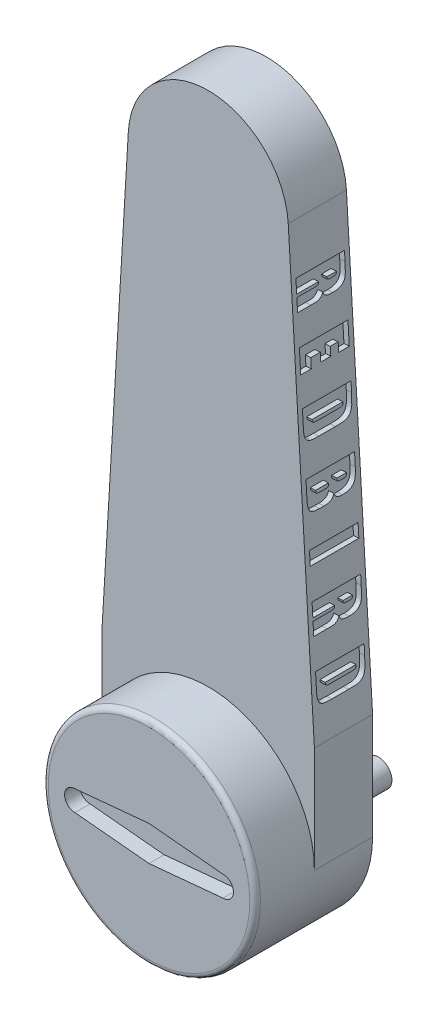
SolidWorks part; units mm, degrees
ref_plane "Front Plane" through (0, 0, 0) normal (0, 0, 1) x (1, 0, 0)
ref_plane "Top Plane" through (0, 0, 0) normal (0, 1, 0) x (1, 0, 0)
ref_plane "Right Plane" through (0, 0, 0) normal (1, 0, 0) x (0, 0, -1)
sketch "Sketch2" plane through (0, 0, 0) normal (0, 0, 1) x (1, 0, 0)
  circle A0 centre (0, 0) radius 39.75
  dimension "D1" = 79.5
extrude "Boss-Extrude1" add sketch "Sketch2" along normal blind 44
sketch "Sketch3" plane through (0, 0, 0) normal (0, 1, 0) x (1, 0, 0)
  line L0 (39.75, -44) -> (39.75, 0) construction
  line L1 (-39.75, 0) -> (39.75, 0)
  line L2 (-39.75, 0) -> (-39.75, -21.8)
  line L3 (-39.75, -21.8) -> (39.75, -21.8)
  line L4 (39.75, 0) -> (39.75, -21.8)
  dimension "D1" = 21.8
extrude "Boss-Extrude2" add sketch "Sketch3" along normal through all
sketch "Sketch4" plane through (0, 0, 0) normal (0, 0, -1) x (-1, 0, 0)
  line L0 (0, 0) -> (0, 203.2) construction
  line L1 (-39.75, 39.75) -> (-29.9473, 204.9767)
  line L2 (39.75, 39.75) -> (29.9473, 204.9767)
  line L3 (-39.75, 39.75) -> (39.75, 39.75)
  circle A0 centre (0, 203.2) radius 30
  circle A1 centre (0, 203.2) radius 25.9
  line M5 (39.75, 39.75) -> (-39.75, 39.75)
  dimension "D2" = 60
  dimension "D3" = 51.8
  dimension "D1" = 203.2
extrude "Boss-Extrude3" add sketch "Sketch4" against normal up to surface (21.8 mm away) contours L0 L2 A0 M5 | L3 L0 A0 L1 | A0 region at (18.2462, 107.3979, 0) region at (-18.2462, 107.3979, 0) region at (21.2148, 183.2065, 0) up to face at (29.2442, 29.2442, 21.8)
sketch "Sketch5" plane through (0, 0, 0) normal (0, 0, -1) x (-1, 0, 0)
  line L0 (-20, 0) -> (20, 0) construction
  line L1 (0, 20) -> (0, -20) construction
  line L2 (0, 0) -> (0, 177.3) construction
  circle A0 centre (-20, 0) radius 5
  circle A1 centre (0, -20) radius 10
  circle A2 centre (0, 20) radius 10
  circle A3 centre (20, 0) radius 5
  circle A4 centre (0, 203.2) radius 25.9 construction
  circle A5 centre (0, 147.3) radius 5
  circle A6 centre (0, 117.3) radius 10
  circle A7 centre (0, -20) radius 5.125
  circle A8 centre (0, 20) radius 5.125
  circle A9 centre (0, 117.3) radius 5.125
  point P5 (0, 0)
  point P9 (0, 0)
  dimension "D3" = 10
  dimension "D4" = 20
  dimension "D7" = 10
  dimension "D8" = 10
  dimension "D9" = 20
  dimension "D10" = 20
  dimension "D11" = 10.25
  dimension "D12" = 10.25
  dimension "D13" = 10.25
  dimension "D1" = 40
  dimension "D2" = 40
  dimension "D5" = 30
  dimension "D6" = 30
extrude "Boss-Extrude4" add sketch "Sketch5" along normal blind 22
extrude "Boss-Extrude5" add sketch "Sketch4<3>" along normal blind 10 from surface contours A1 region at (0, 203.2, 0) starting at face at (0, 92.9045, 21.8)
sketch "Sketch4<3>" plane through (0, 0, 0) normal (0, 0, -1) x (-1, 0, 0) same geometry as "Sketch4"
sketch "Sketch6" plane through (0, 0, 44) normal (0, 0, 1) x (1, 0, 0)
  line L0 (-27.75, 0) -> (27.75, 0) construction
  line L1 (0, -6.5) -> (0, 6.5) construction
  line L2 (-27.75, -3.875) -> (-27.75, 3.875) construction
  line L3 (0, 6.5) -> (-27.75, 3.875)
  line L4 (0, -6.5) -> (-27.75, -3.875)
  line L5 (0, -6.5) -> (27.75, -3.875)
  line L6 (0, 6.5) -> (27.75, 3.875)
  line L7 (27.75, -3.875) -> (27.75, 3.875) construction
  arc A0 (-27.75, -3.875) -> (-27.75, 3.875) centre (-27.75, 0) cw
  arc A1 (27.75, -3.875) -> (27.75, 3.875) centre (27.75, 0) ccw
  point P4 (0, 0)
  point P8 (0, 0)
  point P10 (-27.75, 0)
  point P13 (27.75, 0)
  dimension "D1" = 55.5
  dimension "D2" = 13
  dimension "D3" = 7.75
extrude "Cut-Extrude1" cut sketch "Sketch6" against normal blind 5.67
fillet "Fillet1" radius 2 1 edges at (39.75, 0, 44)
sketch "Sketch7" plane through (41.9606, 2.4895, 0) normal (0.9982, 0.0592, 0) x (0, 0, -1)
  line L0 (-1.8, 184.6917) -> (-1.8, 181.1738)
  line L1 (-11.8422, 116.1491) -> (-16.6583, 116.1491)
  line L2 (-2, 184.4917) -> (-2, 181.1738)
  line L3 (-15.0457, 174.0211) -> (-19.8, 174.0211)
  line L4 (-19.8, 174.0211) -> (-19.8, 178.4187)
  line L5 (-19.8, 178.4187) -> (-13.7794, 178.4187)
  line L6 (-11.6329, 179.8846) -> (-19.8, 179.8846)
  line L7 (-19.8, 179.8846) -> (-19.8, 184.4917)
  line L8 (-19.8, 184.4917) -> (-2, 184.4917)
  line L9 (-4.9318, 179.8846) -> (-8.9106, 179.8846)
  line L10 (-7.2975, 178.4187) -> (-6.3126, 178.4187)
  line L11 (-2, 162.5453) -> (-2, 154.5877)
  line L12 (-2, 154.5877) -> (-5.56, 154.5877)
  line L13 (-5.56, 154.5877) -> (-5.56, 157.9383)
  line L14 (-5.56, 157.9383) -> (-8.9106, 157.9383)
  line L15 (-8.9106, 157.9383) -> (-8.9106, 154.7971)
  line L16 (-8.9106, 154.7971) -> (-12.2612, 154.7971)
  line L17 (-12.2612, 154.7971) -> (-12.2612, 157.9383)
  line L18 (-12.2612, 157.9383) -> (-16.24, 157.9383)
  line L19 (-16.24, 157.9383) -> (-16.24, 154.3783)
  line L20 (-16.24, 154.3783) -> (-19.8, 154.3783)
  line L21 (-19.8, 154.3783) -> (-19.8, 162.5453)
  line L22 (-19.8, 162.5453) -> (-2, 162.5453)
  line L23 (-2, 143.3213) -> (-2, 139.8038)
  line L24 (-8.2791, 132.4319) -> (-14.5124, 132.4319)
  line L25 (-19.8, 137.3923) -> (-19.8, 143.3213)
  line L26 (-19.8, 143.3213) -> (-2, 143.3213)
  line L27 (-4.9318, 138.7143) -> (-16.8682, 138.7143)
  line L28 (-14.2342, 137.039) -> (-7.1829, 137.039)
  line L29 (-2, 120.9561) -> (-2, 116.2346)
  line L30 (-13.8939, 110.0667) -> (-15.566, 110.0667)
  line L31 (-19.8, 115.5441) -> (-19.8, 120.9561)
  line L32 (-19.8, 120.9561) -> (-2, 120.9561)
  line L33 (-4.9318, 116.3491) -> (-8.9106, 116.3491)
  line L34 (-11.6329, 116.3491) -> (-16.8682, 116.3491)
  line L35 (-15.1242, 114.6738) -> (-13.3769, 114.6738)
  line L36 (-2, 93.9839) -> (-19.8, 93.9839)
  line L37 (-19.8, 93.9839) -> (-19.8, 98.591)
  line L38 (-19.8, 98.591) -> (-2, 98.591)
  line L39 (-2, 98.591) -> (-2, 93.9839)
  line L40 (-2, 82.2987) -> (-2, 78.9809)
  line L41 (-15.0457, 71.8281) -> (-19.8, 71.8281)
  line L42 (-19.8, 71.8281) -> (-19.8, 76.2258)
  line L43 (-19.8, 76.2258) -> (-13.7794, 76.2258)
  line L44 (-11.6329, 77.6917) -> (-19.8, 77.6917)
  line L45 (-19.8, 77.6917) -> (-19.8, 82.2987)
  line L46 (-19.8, 82.2987) -> (-2, 82.2987)
  line L47 (-4.9318, 77.6917) -> (-8.9106, 77.6917)
  line L48 (-7.2975, 76.2258) -> (-6.3126, 76.2258)
  line L49 (-2, 60.3524) -> (-2, 56.8349)
  line L50 (-8.2791, 49.463) -> (-14.5124, 49.463)
  line L51 (-19.8, 54.4234) -> (-19.8, 60.3524)
  line L52 (-19.8, 60.3524) -> (-2, 60.3524)
  line L53 (-4.9318, 55.7453) -> (-16.8682, 55.7453)
  line L54 (-14.2342, 54.07) -> (-7.1829, 54.07)
  line L55 (-15.0442, 173.8211) -> (-20, 173.8211)
  line L56 (-20, 173.8211) -> (-20, 178.6187)
  line L57 (-20, 178.6187) -> (-13.7794, 178.6187)
  line L58 (-11.8379, 179.6846) -> (-20, 179.6846)
  line L59 (-20, 179.6846) -> (-20, 184.6917)
  line L60 (-20, 184.6917) -> (-1.8, 184.6917)
  line L61 (-7.2947, 178.6187) -> (-6.3136, 178.6187)
  line L62 (-5.1372, 179.6846) -> (-8.7079, 179.6846)
  line L63 (-20, 162.7453) -> (-1.8, 162.7453)
  line L64 (-1.8, 162.7453) -> (-1.8, 154.3877)
  line L65 (-1.8, 154.3877) -> (-5.76, 154.3877)
  line L66 (-5.76, 154.3877) -> (-5.76, 157.7383)
  line L67 (-5.76, 157.7383) -> (-8.7106, 157.7383)
  line L68 (-8.7106, 157.7383) -> (-8.7106, 154.5971)
  line L69 (-8.7106, 154.5971) -> (-12.4612, 154.5971)
  line L70 (-12.4612, 154.5971) -> (-12.4612, 157.7383)
  line L71 (-12.4612, 157.7383) -> (-16.04, 157.7383)
  line L72 (-16.04, 157.7383) -> (-16.04, 154.1783)
  line L73 (-16.04, 154.1783) -> (-20, 154.1783)
  line L74 (-20, 154.1783) -> (-20, 162.7453)
  line L75 (-20, 143.5213) -> (-1.8, 143.5213)
  line L76 (-1.8, 143.5213) -> (-1.8, 139.8038)
  line L77 (-8.2784, 132.2319) -> (-14.5128, 132.2319)
  line L78 (-20, 137.3909) -> (-20, 143.5213)
  line L79 (-15.1267, 114.8738) -> (-13.3758, 114.8738)
  line L80 (-5.1361, 116.1491) -> (-8.7058, 116.1491)
  line L81 (-20, 98.791) -> (-1.8, 98.791)
  line L82 (-1.8, 98.791) -> (-1.8, 93.7839)
  line L83 (-5.1349, 138.5143) -> (-16.6645, 138.5143)
  line L84 (-14.2351, 137.239) -> (-7.1805, 137.239)
  line L85 (-20, 121.1561) -> (-1.8, 121.1561)
  line L86 (-1.8, 121.1561) -> (-1.8, 116.2334)
  line L87 (-13.8936, 109.8667) -> (-15.566, 109.8667)
  line L88 (-20, 115.5431) -> (-20, 121.1561)
  line L89 (-1.8, 93.7839) -> (-20, 93.7839)
  line L90 (-20, 93.7839) -> (-20, 98.791)
  line L91 (-20, 82.4987) -> (-1.8, 82.4987)
  line L92 (-1.8, 82.4987) -> (-1.8, 78.9809)
  line L93 (-15.0442, 71.6281) -> (-20, 71.6281)
  line L94 (-20, 71.6281) -> (-20, 76.4258)
  line L95 (-20, 76.4258) -> (-13.7794, 76.4258)
  line L96 (-11.8379, 77.4917) -> (-20, 77.4917)
  line L97 (-20, 77.4917) -> (-20, 82.4987)
  line L98 (-7.2947, 76.4258) -> (-6.3136, 76.4258)
  line L99 (-5.1372, 77.4917) -> (-8.7079, 77.4917)
  line L100 (-14.2351, 54.27) -> (-7.1805, 54.27)
  line L101 (-5.1349, 55.5453) -> (-16.6645, 55.5453)
  line L102 (-20, 54.4219) -> (-20, 60.5524)
  line L103 (-20, 60.5524) -> (-1.8, 60.5524)
  line L104 (-1.8, 60.5524) -> (-1.8, 56.8349)
  line L105 (-8.2784, 49.263) -> (-14.5128, 49.263)
  spline S0 degree 3 poles (-2, 181.1738) (-1.9981, 180.6655) (-2.0068, 179.9357) (-2.034, 179.0075) (-2.0583, 178.4118) (-2.0946, 177.8838) (-2.1365, 177.4223) (-2.1832, 177.0267) (-2.2422, 176.6885) (-2.3184, 176.3914) (-2.4187, 176.1172) (-2.5379, 175.8548) (-2.6869, 175.6074) (-2.8617, 175.3763) (-3.0552, 175.1541) (-3.2763, 174.948) (-3.5217, 174.7536) (-3.7998, 174.5772) (-4.1159, 174.4286) (-4.4681, 174.2996) (-4.8602, 174.2012) (-5.2883, 174.1194) (-5.9348, 174.0377) (-6.4412, 174.0257) (-6.7903, 174.0211) knots 0 0 0 0 0.148543 0.213274 0.27134 0.322776 0.367908 0.406771 0.439156 0.468147 0.496277 0.524371 0.552249 0.580489 0.608944 0.638258 0.668673 0.700331 0.734261 0.77056 0.809755 0.852263 0.897886 1 1 1 1
  spline S1 degree 3 poles (-6.7903, 174.0211) (-7.1039, 174.0159) (-7.5537, 174.0372) (-8.1248, 174.0861) (-8.4902, 174.1472) (-8.8148, 174.2161) (-9.0987, 174.3045) (-9.3418, 174.4065) (-9.5475, 174.5307) (-9.7181, 174.6841) (-9.8698, 174.8618) (-10.0023, 175.0725) (-10.1145, 175.3152) (-10.2133, 175.5875) (-10.3205, 176.0108) (-10.3706, 176.3476) (-10.3896, 176.5831) knots 0 0 0 0 0.183754 0.264085 0.33602 0.400896 0.458558 0.510133 0.555226 0.598736 0.644114 0.691853 0.744219 0.800677 0.861499 1 1 1 1
  spline S2 degree 3 poles (-10.3896, 176.5831) (-10.4477, 176.3705) (-10.53, 176.0622) (-10.6742, 175.6791) (-10.7897, 175.4345) (-10.9067, 175.215) (-11.0338, 175.0254) (-11.1684, 174.8627) (-11.3529, 174.6892) (-11.5852, 174.5151) (-11.8564, 174.3409) (-12.1197, 174.2167) (-12.3412, 174.1385) (-12.543, 174.1055) (-12.7439, 174.0834) (-12.9983, 174.0648) (-13.3059, 174.0488) (-13.6659, 174.0363) (-14.2516, 174.0213) (-14.7174, 174.0259) (-15.0457, 174.0211) knots 0 0 0 0 0.110219 0.159211 0.20432 0.245296 0.283389 0.318211 0.350594 0.409678 0.463061 0.511332 0.554938 0.579849 0.613314 0.655951 0.707257 0.767249 0.835943 1 1 1 1
  spline S3 degree 3 poles (-13.7794, 178.4187) (-13.5603, 178.4206) (-13.2487, 178.4204) (-12.8563, 178.4494) (-12.6138, 178.474) (-12.4051, 178.5065) (-12.2319, 178.5444) (-12.0913, 178.5887) (-11.9798, 178.6452) (-11.8926, 178.722) (-11.8245, 178.8214) (-11.7614, 178.9389) (-11.7129, 179.0826) (-11.6789, 179.2498) (-11.6423, 179.519) (-11.6342, 179.7339) (-11.6329, 179.8846) knots 0 0 0 0 0.208642 0.296034 0.374307 0.440504 0.496897 0.54284 0.580443 0.615002 0.652158 0.694401 0.741661 0.795804 0.856563 1 1 1 1
  spline S4 degree 3 poles (-8.9106, 179.8846) (-8.9127, 179.6528) (-8.8925, 179.3307) (-8.8017, 178.9494) (-8.7231, 178.769) (-8.6251, 178.6601) (-8.5222, 178.5947) (-8.3901, 178.5409) (-8.2286, 178.4959) (-8.038, 178.4611) (-7.7252, 178.4234) (-7.474, 178.4237) (-7.2975, 178.4187) knots 0 0 0 0 0.263059 0.362536 0.443753 0.482229 0.526771 0.580464 0.643421 0.71635 0.799709 1 1 1 1
  spline S5 degree 3 poles (-6.3126, 178.4187) (-6.0777, 178.4211) (-5.7485, 178.4373) (-5.374, 178.5775) (-5.1844, 178.7238) (-5.0685, 178.9346) (-4.9447, 179.3168) (-4.9363, 179.6497) (-4.9318, 179.8846) knots 0 0 0 0 0.296724 0.405999 0.497474 0.590179 0.702697 1 1 1 1
  spline S6 degree 3 poles (-2, 139.8038) (-1.9956, 139.2824) (-2.0094, 138.534) (-2.0395, 137.583) (-2.0704, 136.9718) (-2.117, 136.4308) (-2.1678, 135.957) (-2.2277, 135.5525) (-2.3206, 135.1143) (-2.4728, 134.6455) (-2.6938, 134.1448) (-2.9758, 133.7187) (-3.306, 133.3657) (-3.6705, 133.0823) (-4.0556, 132.8554) (-4.4605, 132.687) (-4.8224, 132.5944) (-5.145, 132.5497) (-5.4395, 132.5163) (-5.7856, 132.4926) (-6.1836, 132.4682) (-6.6332, 132.4541) (-7.3377, 132.4339) (-7.8919, 132.4347) (-8.2791, 132.4319) knots 0 0 0 0 0.131289 0.188445 0.2396 0.285351 0.325141 0.359593 0.388249 0.437842 0.483436 0.525634 0.565855 0.604586 0.641514 0.678082 0.71465 0.735196 0.760065 0.789259 0.822545 0.860469 0.902502 1 1 1 1
  spline S7 degree 3 poles (-14.5124, 132.4319) (-14.8788, 132.4334) (-15.4037, 132.4345) (-16.0701, 132.4621) (-16.4954, 132.4892) (-16.8711, 132.5159) (-17.1978, 132.5544) (-17.4737, 132.6035) (-17.7737, 132.6699) (-18.0937, 132.7877) (-18.4383, 132.9635) (-18.7347, 133.1895) (-18.9908, 133.4536) (-19.2002, 133.7606) (-19.376, 134.0986) (-19.5222, 134.4686) (-19.6098, 134.8037) (-19.666, 135.0966) (-19.7004, 135.3469) (-19.7347, 135.6226) (-19.7552, 135.9263) (-19.7747, 136.2546) (-19.7999, 136.7463) (-19.7961, 137.1285) (-19.8, 137.3923) knots 0 0 0 0 0.124488 0.178251 0.226503 0.269237 0.306181 0.338157 0.364398 0.41045 0.453534 0.495323 0.536458 0.577977 0.621061 0.66564 0.712819 0.738467 0.766915 0.798622 0.832803 0.870286 0.91034 1 1 1 1
  spline S8 degree 3 poles (-16.8682, 138.7143) (-16.8674, 138.5419) (-16.8597, 138.2945) (-16.8125, 137.9868) (-16.774, 137.7943) (-16.7118, 137.6326) (-16.647, 137.4922) (-16.5606, 137.3829) (-16.4579, 137.2963) (-16.325, 137.2337) (-16.1549, 137.1834) (-15.9413, 137.1388) (-15.6846, 137.1004) (-15.3843, 137.0715) (-14.8966, 137.0461) (-14.5081, 137.0366) (-14.2342, 137.039) knots 0 0 0 0 0.137111 0.195798 0.247293 0.292517 0.333199 0.369595 0.402207 0.439014 0.485321 0.542924 0.61215 0.691372 0.782487 1 1 1 1
  spline S9 degree 3 poles (-7.1829, 137.039) (-6.9964, 137.0344) (-6.7303, 137.0433) (-6.3932, 137.051) (-6.1815, 137.06) (-5.9985, 137.0747) (-5.8429, 137.0846) (-5.7157, 137.1062) (-5.582, 137.1289) (-5.443, 137.1804) (-5.2977, 137.2649) (-5.1805, 137.3845) (-5.0837, 137.5372) (-5.0121, 137.741) (-4.9386, 138.1366) (-4.9349, 138.4712) (-4.9318, 138.7143) knots 0 0 0 0 0.161879 0.231001 0.29259 0.34573 0.390378 0.427726 0.457613 0.507913 0.555475 0.602325 0.65169 0.711291 0.788512 1 1 1 1
  spline S10 degree 3 poles (-2, 116.2346) (-2.004, 115.8844) (-2.0071, 115.3757) (-2.042, 114.7201) (-2.0831, 114.2796) (-2.1261, 113.872) (-2.1857, 113.4989) (-2.2533, 113.1591) (-2.3315, 112.8491) (-2.428, 112.5637) (-2.5413, 112.2943) (-2.6802, 112.0405) (-2.8415, 111.8018) (-3.0217, 111.574) (-3.2259, 111.3622) (-3.4483, 111.1608) (-3.6966, 110.9765) (-3.9726, 110.805) (-4.2921, 110.6683) (-4.6448, 110.5411) (-5.0405, 110.4471) (-5.4714, 110.3665) (-6.1256, 110.2999) (-6.6357, 110.27) (-6.9899, 110.2761) knots 0 0 0 0 0.114386 0.166124 0.214411 0.258869 0.299987 0.337788 0.372007 0.404341 0.436105 0.467354 0.498678 0.530114 0.562118 0.594663 0.628011 0.663022 0.700498 0.741288 0.785356 0.833155 0.88442 1 1 1 1
  spline S11 degree 3 poles (-6.9899, 110.2761) (-7.227, 110.2723) (-7.5686, 110.2901) (-8.0022, 110.3443) (-8.2864, 110.3943) (-8.5399, 110.4664) (-8.7663, 110.5513) (-8.964, 110.6518) (-9.1363, 110.7725) (-9.2872, 110.9181) (-9.4253, 111.0915) (-9.5554, 111.2929) (-9.6721, 111.5272) (-9.7889, 111.7874) (-9.924, 112.1979) (-10.0157, 112.5216) (-10.0624, 112.7498) knots 0 0 0 0 0.159593 0.229912 0.29415 0.353664 0.407126 0.456721 0.502563 0.548271 0.597357 0.65154 0.709345 0.77347 0.843372 1 1 1 1
  spline S12 degree 3 poles (-10.0624, 112.7498) (-10.1183, 112.5059) (-10.2185, 112.155) (-10.399, 111.7216) (-10.5418, 111.4376) (-10.7034, 111.1867) (-10.8795, 110.9669) (-11.0712, 110.7773) (-11.2803, 110.6181) (-11.5114, 110.4844) (-11.7699, 110.3755) (-12.0528, 110.2751) (-12.3685, 110.2033) (-12.7087, 110.1399) (-13.2206, 110.0833) (-13.6187, 110.0677) (-13.8939, 110.0667) knots 0 0 0 0 0.14404 0.209305 0.269928 0.326675 0.380677 0.43171 0.481413 0.531464 0.584861 0.642612 0.703952 0.770914 0.841672 1 1 1 1
  spline S13 degree 3 poles (-15.566, 110.0667) (-15.8508, 110.0669) (-16.2639, 110.0774) (-16.7938, 110.1221) (-17.1478, 110.1668) (-17.4717, 110.2267) (-17.768, 110.2926) (-18.0337, 110.3781) (-18.3432, 110.5062) (-18.6861, 110.7034) (-19.0241, 111.0158) (-19.3008, 111.3821) (-19.4658, 111.7453) (-19.5628, 112.086) (-19.6261, 112.4046) (-19.682, 112.7823) (-19.7208, 113.2195) (-19.7579, 113.7157) (-19.7943, 114.4967) (-19.7954, 115.1134) (-19.8, 115.5441) knots 0 0 0 0 0.102225 0.148189 0.190817 0.230204 0.266378 0.299678 0.330209 0.386533 0.440563 0.494267 0.550311 0.582518 0.621285 0.666789 0.719486 0.778749 0.845365 1 1 1 1
  spline S14 degree 2 poles (-8.9106, 116.3491) (-8.9038, 116.0939) (-8.9008, 115.8386) knots 0 0 0 1 1 1
  spline S15 degree 3 poles (-8.9008, 115.8386) (-8.9036, 115.6319) (-8.8787, 115.3414) (-8.7282, 115.0182) (-8.5926, 114.8871) (-8.4492, 114.824) (-8.3051, 114.7827) (-8.1215, 114.7526) (-7.9002, 114.7227) (-7.638, 114.701) (-7.2116, 114.6784) (-6.8721, 114.6739) (-6.6332, 114.6738) knots 0 0 0 0 0.207123 0.283932 0.350841 0.389257 0.439129 0.499893 0.574453 0.661745 0.761896 1 1 1 1
  spline S16 degree 3 poles (-6.6332, 114.6738) (-6.3937, 114.6721) (-6.0649, 114.6867) (-5.6703, 114.757) (-5.4631, 114.8337) (-5.3036, 114.9277) (-5.1808, 115.0341) (-5.0833, 115.1501) (-5.0215, 115.2942) (-4.9847, 115.475) (-4.9423, 115.8295) (-4.9357, 116.1287) (-4.9318, 116.3491) knots 0 0 0 0 0.247841 0.339943 0.41354 0.475302 0.530527 0.581127 0.630646 0.690893 0.771688 1 1 1 1
  spline S17 degree 3 poles (-16.8682, 116.3491) (-16.8607, 116.1854) (-16.8509, 115.9506) (-16.8087, 115.6568) (-16.7744, 115.4715) (-16.7282, 115.3109) (-16.6771, 115.1734) (-16.6194, 115.0592) (-16.5473, 114.9684) (-16.4559, 114.897) (-16.3441, 114.8341) (-16.2026, 114.7873) (-16.0376, 114.7452) (-15.846, 114.7129) (-15.5394, 114.6828) (-15.2958, 114.6696) (-15.1242, 114.6738) knots 0 0 0 0 0.168587 0.241054 0.305045 0.362185 0.41258 0.455716 0.49319 0.530665 0.574337 0.624343 0.683356 0.749349 0.823768 1 1 1 1
  spline S18 degree 3 poles (-13.3769, 114.6738) (-13.1968, 114.6716) (-12.9412, 114.6806) (-12.6194, 114.7069) (-12.4221, 114.7341) (-12.2551, 114.7745) (-12.1175, 114.8188) (-12.0065, 114.8697) (-11.9197, 114.9351) (-11.8601, 115.0258) (-11.8035, 115.1333) (-11.7595, 115.2708) (-11.721, 115.4339) (-11.689, 115.6242) (-11.6524, 115.9315) (-11.6392, 116.1765) (-11.6329, 116.3491) knots 0 0 0 0 0.182369 0.25887 0.326977 0.383772 0.432672 0.473181 0.506991 0.541018 0.58202 0.629874 0.686669 0.751678 0.825111 1 1 1 1
  spline S19 degree 3 poles (-2, 78.9809) (-1.9981, 78.4725) (-2.0068, 77.7427) (-2.034, 76.8146) (-2.0583, 76.2188) (-2.0946, 75.6909) (-2.1365, 75.2293) (-2.1832, 74.8337) (-2.2422, 74.4956) (-2.3184, 74.1985) (-2.4187, 73.9243) (-2.5379, 73.6619) (-2.6869, 73.4144) (-2.8617, 73.1834) (-3.0552, 72.9611) (-3.2763, 72.7551) (-3.5217, 72.5607) (-3.7998, 72.3842) (-4.1159, 72.2357) (-4.4681, 72.1066) (-4.8602, 72.0083) (-5.2883, 71.9265) (-5.9348, 71.8448) (-6.4412, 71.8328) (-6.7903, 71.8281) knots 0 0 0 0 0.148543 0.213274 0.27134 0.322776 0.367908 0.406771 0.439156 0.468147 0.496277 0.524371 0.552249 0.580489 0.608944 0.638258 0.668673 0.700331 0.734261 0.77056 0.809755 0.852263 0.897886 1 1 1 1
  spline S20 degree 3 poles (-6.7903, 71.8281) (-7.1039, 71.8229) (-7.5537, 71.8442) (-8.1248, 71.8931) (-8.4902, 71.9543) (-8.8148, 72.0232) (-9.0987, 72.1116) (-9.3418, 72.2136) (-9.5475, 72.3378) (-9.7181, 72.4912) (-9.8698, 72.6688) (-10.0023, 72.8796) (-10.1145, 73.1223) (-10.2133, 73.3946) (-10.3205, 73.8178) (-10.3706, 74.1547) (-10.3896, 74.3902) knots 0 0 0 0 0.183754 0.264085 0.33602 0.400896 0.458558 0.510133 0.555226 0.598736 0.644114 0.691853 0.744219 0.800677 0.861499 1 1 1 1
  spline S21 degree 3 poles (-10.3896, 74.3902) (-10.4477, 74.1775) (-10.53, 73.8692) (-10.6742, 73.4862) (-10.7897, 73.2416) (-10.9067, 73.0221) (-11.0338, 72.8325) (-11.1684, 72.6697) (-11.3529, 72.4963) (-11.5852, 72.3221) (-11.8564, 72.1479) (-12.1197, 72.0237) (-12.3412, 71.9456) (-12.543, 71.9126) (-12.7439, 71.8905) (-12.9983, 71.8719) (-13.3059, 71.8559) (-13.6659, 71.8434) (-14.2516, 71.8283) (-14.7174, 71.8329) (-15.0457, 71.8281) knots 0 0 0 0 0.110219 0.159211 0.20432 0.245296 0.283389 0.318211 0.350594 0.409678 0.463061 0.511332 0.554938 0.579849 0.613314 0.655951 0.707257 0.767249 0.835943 1 1 1 1
  spline S22 degree 3 poles (-13.7794, 76.2258) (-13.5603, 76.2277) (-13.2487, 76.2274) (-12.8563, 76.2565) (-12.6138, 76.281) (-12.4051, 76.3136) (-12.2319, 76.3515) (-12.0913, 76.3957) (-11.9798, 76.4522) (-11.8926, 76.5291) (-11.8245, 76.6284) (-11.7614, 76.746) (-11.7129, 76.8897) (-11.6789, 77.0569) (-11.6423, 77.3261) (-11.6342, 77.541) (-11.6329, 77.6917) knots 0 0 0 0 0.208642 0.296034 0.374307 0.440504 0.496897 0.54284 0.580443 0.615002 0.652158 0.694401 0.741661 0.795804 0.856563 1 1 1 1
  spline S23 degree 3 poles (-8.9106, 77.6917) (-8.9127, 77.4599) (-8.8925, 77.1377) (-8.8017, 76.7565) (-8.7231, 76.5761) (-8.6251, 76.4671) (-8.5222, 76.4017) (-8.3901, 76.3479) (-8.2286, 76.3029) (-8.038, 76.2681) (-7.7252, 76.2304) (-7.474, 76.2307) (-7.2975, 76.2258) knots 0 0 0 0 0.263059 0.362536 0.443753 0.482229 0.526771 0.580464 0.643421 0.71635 0.799709 1 1 1 1
  spline S24 degree 3 poles (-6.3126, 76.2258) (-6.0777, 76.2281) (-5.7485, 76.2444) (-5.374, 76.3846) (-5.1844, 76.5309) (-5.0685, 76.7416) (-4.9447, 77.1238) (-4.9363, 77.4568) (-4.9318, 77.6917) knots 0 0 0 0 0.296724 0.405999 0.497474 0.590179 0.702697 1 1 1 1
  spline S25 degree 3 poles (-2, 56.8349) (-1.9956, 56.3134) (-2.0094, 55.5651) (-2.0395, 54.614) (-2.0704, 54.0028) (-2.117, 53.4619) (-2.1678, 52.988) (-2.2277, 52.5836) (-2.3206, 52.1454) (-2.4728, 51.6765) (-2.6938, 51.1759) (-2.9758, 50.7498) (-3.306, 50.3968) (-3.6705, 50.1134) (-4.0556, 49.8865) (-4.4605, 49.7181) (-4.8224, 49.6255) (-5.145, 49.5808) (-5.4395, 49.5474) (-5.7856, 49.5236) (-6.1836, 49.4993) (-6.6332, 49.4852) (-7.3377, 49.4649) (-7.8919, 49.4658) (-8.2791, 49.463) knots 0 0 0 0 0.131289 0.188445 0.2396 0.285351 0.325141 0.359593 0.388249 0.437842 0.483436 0.525634 0.565855 0.604586 0.641514 0.678082 0.71465 0.735196 0.760065 0.789259 0.822545 0.860469 0.902502 1 1 1 1
  spline S26 degree 3 poles (-14.5124, 49.463) (-14.8788, 49.4645) (-15.4037, 49.4656) (-16.0701, 49.4931) (-16.4954, 49.5203) (-16.8711, 49.547) (-17.1978, 49.5855) (-17.4737, 49.6346) (-17.7737, 49.701) (-18.0937, 49.8187) (-18.4383, 49.9945) (-18.7347, 50.2205) (-18.9908, 50.4847) (-19.2002, 50.7917) (-19.376, 51.1296) (-19.5222, 51.4997) (-19.6098, 51.8348) (-19.666, 52.1277) (-19.7004, 52.378) (-19.7347, 52.6537) (-19.7552, 52.9574) (-19.7747, 53.2857) (-19.7999, 53.7774) (-19.7961, 54.1595) (-19.8, 54.4234) knots 0 0 0 0 0.124488 0.178251 0.226503 0.269237 0.306181 0.338157 0.364398 0.41045 0.453534 0.495323 0.536458 0.577977 0.621061 0.66564 0.712819 0.738467 0.766915 0.798622 0.832803 0.870286 0.91034 1 1 1 1
  spline S27 degree 3 poles (-16.8682, 55.7453) (-16.8674, 55.573) (-16.8597, 55.3256) (-16.8125, 55.0179) (-16.774, 54.8254) (-16.7118, 54.6636) (-16.647, 54.5232) (-16.5606, 54.4139) (-16.4579, 54.3274) (-16.325, 54.2647) (-16.1549, 54.2144) (-15.9413, 54.1699) (-15.6846, 54.1315) (-15.3843, 54.1025) (-14.8966, 54.0772) (-14.5081, 54.0677) (-14.2342, 54.07) knots 0 0 0 0 0.137111 0.195798 0.247293 0.292517 0.333199 0.369595 0.402207 0.439014 0.485321 0.542924 0.61215 0.691372 0.782487 1 1 1 1
  spline S28 degree 3 poles (-7.1829, 54.07) (-6.9964, 54.0655) (-6.7303, 54.0744) (-6.3932, 54.0821) (-6.1815, 54.0911) (-5.9985, 54.1058) (-5.8429, 54.1156) (-5.7157, 54.1373) (-5.582, 54.1599) (-5.443, 54.2115) (-5.2977, 54.296) (-5.1805, 54.4156) (-5.0837, 54.5683) (-5.0121, 54.7721) (-4.9386, 55.1676) (-4.9349, 55.5022) (-4.9318, 55.7453) knots 0 0 0 0 0.161879 0.231001 0.29259 0.34573 0.390378 0.427726 0.457613 0.507913 0.555475 0.602325 0.65169 0.711291 0.788512 1 1 1 1
  spline S29 degree 1 poles (-1.8, 181.1738) (-6.7873, 173.8211) knots 0 0 1 1 construction
  spline S30 degree 1 poles (-6.7873, 173.8211) (-10.4498, 175.7107) knots 0 0 1 1 construction
  spline S31 degree 1 poles (-10.4498, 175.7107) (-15.0442, 173.8211) knots 0 0 1 1 construction
  spline S32 degree 1 poles (-13.7794, 178.6187) (-11.8379, 179.6846) knots 0 0 1 1 construction
  spline S33 degree 3 poles (-1.8, 181.1738) (-1.7968, 180.3152) (-1.8179, 179.0237) (-1.9251, 177.3173) (-2.1534, 175.9722) (-2.9767, 174.8255) (-4.1703, 174.1131) (-5.4878, 173.8607) (-6.3523, 173.8269) (-6.7873, 173.8211) knots 0.000072 0.000072 0.000072 0.000072 0.250046 0.375033 0.50002 0.625007 0.749994 0.874981 0.999968 0.999968 0.999968 0.999968
  spline S34 degree 3 poles (-6.7873, 173.8211) (-7.1505, 173.8151) (-7.8758, 173.846) (-8.7843, 173.9782) (-9.5172, 174.2381) (-9.9972, 174.6501) (-10.2858, 175.1709) (-10.4037, 175.5272) (-10.4498, 175.7107) knots 0.000063 0.000063 0.000063 0.000063 0.209226 0.418389 0.52297 0.627551 0.732133 0.836714 0.836714 0.836714 0.836714
  spline S35 degree 3 poles (-10.4498, 175.7107) (-10.5319, 175.4992) (-10.7143, 175.0904) (-11.1891, 174.5283) (-11.6619, 174.2161) (-12.074, 174.0121) (-12.5607, 173.8771) (-13.0976, 173.8618) (-13.9687, 173.8193) (-14.6128, 173.8274) (-15.0442, 173.8211) knots 0.139503 0.139503 0.139503 0.139503 0.247096 0.354688 0.462281 0.516077 0.569873 0.677466 0.785059 1.000244 1.000244 1.000244 1.000244
  spline S36 degree 3 poles (-13.7794, 178.6187) (-13.5379, 178.6208) (-13.1732, 178.6225) (-12.6975, 178.6636) (-12.3477, 178.7163) (-12.0997, 178.791) (-12.0153, 178.8911) (-11.9139, 179.0732) (-11.8651, 179.3308) (-11.8429, 179.569) (-11.8379, 179.6846) knots 0.000547 0.000547 0.000547 0.000547 0.233854 0.350508 0.467161 0.583815 0.642142 0.700469 0.817122 0.933776 0.933776 0.933776 0.933776
  spline S37 degree 1 poles (-8.7079, 179.6846) (-7.2947, 178.6187) knots 0 0 1 1 construction
  spline S38 degree 1 poles (-6.3136, 178.6187) (-5.1372, 179.6846) knots 0 0 1 1 construction
  spline S39 degree 3 poles (-8.7079, 179.6846) (-8.7006, 179.4953) (-8.6697, 179.2014) (-8.5564, 178.8616) (-8.4393, 178.7665) (-8.1681, 178.6829) (-7.7971, 178.6266) (-7.4922, 178.6242) (-7.2947, 178.6187) knots 0.078446 0.078446 0.078446 0.078446 0.308574 0.423638 0.538703 0.653767 0.768831 0.99896 0.99896 0.99896 0.99896
  spline S40 degree 3 poles (-6.3136, 178.6187) (-6.1432, 178.6205) (-5.7914, 178.6357) (-5.4146, 178.7636) (-5.2786, 178.954) (-5.1659, 179.2615) (-5.1439, 179.5177) (-5.1372, 179.6846) knots 0.000432 0.000432 0.000432 0.000432 0.228515 0.456599 0.57064 0.684682 0.912765 0.912765 0.912765 0.912765
  spline S41 degree 1 poles (-1.8, 139.8038) (-8.2784, 132.2319) knots 0 0 1 1 construction
  spline S42 degree 1 poles (-14.5128, 132.2319) (-20, 137.3909) knots 0 0 1 1 construction
  spline S43 degree 3 poles (-1.8, 139.8038) (-1.7958, 139.3051) (-1.8118, 138.3079) (-1.8712, 136.8114) (-2.0132, 135.3082) (-2.5341, 133.7958) (-3.5287, 132.8634) (-4.5086, 132.4366) (-5.546, 132.286) (-6.7833, 132.2431) (-7.7806, 132.2355) (-8.2784, 132.2319) knots 0.000141 0.000141 0.000141 0.000141 0.125131 0.250121 0.375111 0.500101 0.625091 0.687586 0.750081 0.875071 1.000061 1.000061 1.000061 1.000061
  spline S44 degree 3 poles (-14.5128, 132.2319) (-14.8826, 132.2334) (-15.6234, 132.2359) (-16.7267, 132.2954) (-17.875, 132.4199) (-18.9689, 133.0053) (-19.6287, 134.03) (-20.0023, 135.5434) (-19.9889, 136.6467) (-20, 137.3909) knots -0.000046 -0.000046 -0.000046 -0.000046 0.12498 0.250007 0.375034 0.500061 0.625088 0.750115 1.000168 1.000168 1.000168 1.000168
  spline S45 degree 1 poles (-16.6645, 138.5143) (-14.2351, 137.239) knots 0 0 1 1 construction
  spline S46 degree 1 poles (-7.1805, 137.239) (-5.1349, 138.5143) knots 0 0 1 1 construction
  spline S47 degree 3 poles (-16.6645, 138.5143) (-16.6549, 138.2425) (-16.5903, 137.7684) (-16.3746, 137.4361) (-15.979, 137.3463) (-15.5519, 137.2829) (-14.9722, 137.2479) (-14.5288, 137.2365) (-14.2351, 137.239) knots 0.054835 0.054835 0.054835 0.054835 0.291183 0.409356 0.52753 0.645704 0.763877 1.000225 1.000225 1.000225 1.000225
  spline S48 degree 3 poles (-7.1805, 137.239) (-6.9133, 137.2324) (-6.5145, 137.2433) (-5.9743, 137.274) (-5.4777, 137.321) (-5.1641, 137.691) (-5.1404, 138.2611) (-5.1349, 138.5143) knots -0.000707 -0.000707 -0.000707 -0.000707 0.234678 0.35237 0.470063 0.705448 0.940832 0.940832 0.940832 0.940832
  spline S49 degree 1 poles (-1.8, 116.2334) (-6.99, 110.0761) knots 0 0 1 1 construction
  spline S50 degree 1 poles (-6.99, 110.0761) (-10.0704, 112.0069) knots 0 0 1 1 construction
  spline S51 degree 1 poles (-10.0704, 112.0069) (-13.8936, 109.8667) knots 0 0 1 1 construction
  spline S52 degree 1 poles (-15.566, 109.8667) (-20, 115.5431) knots 0 0 1 1 construction
  spline S53 degree 3 poles (-1.8, 116.2334) (-1.8088, 115.4614) (-1.8401, 114.3118) (-2.0956, 112.7541) (-2.6313, 111.6344) (-3.5131, 110.774) (-4.6533, 110.2833) (-5.822, 110.1138) (-6.6002, 110.0695) (-6.99, 110.0761) knots -0.000124 -0.000124 -0.000124 -0.000124 0.249818 0.37479 0.499761 0.624733 0.749704 0.874675 0.999647 0.999647 0.999647 0.999647
  spline S54 degree 3 poles (-6.99, 110.0761) (-7.312, 110.0711) (-7.9517, 110.1166) (-8.7632, 110.2798) (-9.3747, 110.6829) (-9.7895, 111.2431) (-9.9715, 111.6939) (-10.0704, 112.0069) knots 0.000725 0.000725 0.000725 0.000725 0.210879 0.421033 0.526109 0.631186 0.84134 0.84134 0.84134 0.84134
  spline S55 degree 3 poles (-10.0704, 112.0069) (-10.2054, 111.6347) (-10.4643, 111.0975) (-11.05, 110.5045) (-11.7834, 110.1134) (-12.7424, 109.9053) (-13.5091, 109.8681) (-13.8936, 109.8667) knots 0.134809 0.134809 0.134809 0.134809 0.351124 0.459281 0.567439 0.783754 1.000069 1.000069 1.000069 1.000069
  spline S56 degree 3 poles (-15.566, 109.8667) (-15.9199, 109.8669) (-16.6274, 109.8911) (-17.6854, 110.0284) (-18.7571, 110.4201) (-19.5689, 111.2894) (-19.8558, 112.394) (-19.9434, 113.4398) (-19.9958, 114.4982) (-19.9963, 115.194) (-20, 115.5431) knots -0.000007 -0.000007 -0.000007 -0.000007 0.12501 0.250027 0.375044 0.500061 0.625078 0.750095 0.875112 1.000128 1.000128 1.000128 1.000128
  spline S57 degree 1 poles (-13.3758, 114.8738) (-11.8422, 116.1491) knots 0 0 1 1 construction
  spline S58 degree 1 poles (-16.6583, 116.1491) (-15.1267, 114.8738) knots 0 0 1 1 construction
  spline S59 degree 3 poles (-13.3758, 114.8738) (-13.1534, 114.8711) (-12.8062, 114.8872) (-12.3997, 114.9335) (-12.1238, 115.0304) (-12.062, 115.0752) (-11.9671, 115.2437) (-11.8898, 115.5839) (-11.8543, 115.9293) (-11.8422, 116.1491) knots -0.000403 -0.000403 -0.000403 -0.000403 0.231868 0.348003 0.464139 0.522206 0.580274 0.696409 0.92868 0.92868 0.92868 0.92868
  spline S60 degree 3 poles (-16.6583, 116.1491) (-16.6463, 115.9357) (-16.6156, 115.6132) (-16.4861, 115.2061) (-16.3158, 114.9999) (-15.7737, 114.8923) (-15.3428, 114.8685) (-15.1267, 114.8738) knots 0.072465 0.072465 0.072465 0.072465 0.304559 0.420606 0.536653 0.768747 1.000841 1.000841 1.000841 1.000841
  spline S61 degree 1 poles (-8.7008, 115.8384) (-6.6325, 114.8738) knots 0 0 1 1 construction
  spline S62 degree 1 poles (-6.6325, 114.8738) (-5.1361, 116.1491) knots 0 0 1 1 construction
  spline S63 degree 1 poles (-8.7058, 116.1491) (-8.7008, 115.8384) knots 0 0 1 1 construction
  spline S64 degree 3 poles (-8.7008, 115.8384) (-8.7038, 115.6216) (-8.645, 115.222) (-8.4539, 115.0161) (-8.1087, 114.9493) (-7.7461, 114.9074) (-7.2547, 114.8795) (-6.8807, 114.8739) (-6.6325, 114.8738) knots -0.000853 -0.000853 -0.000853 -0.000853 0.249415 0.374549 0.499684 0.624818 0.749952 1.00022 1.00022 1.00022 1.00022
  spline S65 degree 3 poles (-6.6325, 114.8738) (-6.4172, 114.8723) (-5.9722, 114.8867) (-5.4926, 115.0138) (-5.2371, 115.247) (-5.163, 115.5728) (-5.1419, 115.9336) (-5.1361, 116.1491) knots -0.000229 -0.000229 -0.000229 -0.000229 0.232103 0.464435 0.580601 0.696767 0.9291 0.9291 0.9291 0.9291
  spline S66 degree 2 poles (-8.7058, 116.1491) (-8.7026, 115.9937) (-8.7008, 115.8384) knots 0.399977 0.399977 0.399977 1.005003 1.005003 1.005003
  spline S67 degree 1 poles (-1.8, 78.9809) (-6.7873, 71.6282) knots 0 0 1 1 construction
  spline S68 degree 1 poles (-6.7873, 71.6282) (-10.4498, 73.5178) knots 0 0 1 1 construction
  spline S69 degree 1 poles (-10.4498, 73.5178) (-15.0442, 71.6281) knots 0 0 1 1 construction
  spline S70 degree 1 poles (-13.7794, 76.4258) (-11.8379, 77.4917) knots 0 0 1 1 construction
  spline S71 degree 3 poles (-1.8, 78.9809) (-1.7968, 78.1222) (-1.8179, 76.8308) (-1.9251, 75.1243) (-2.1534, 73.7793) (-2.9767, 72.6325) (-4.1703, 71.9201) (-5.4878, 71.6678) (-6.3523, 71.634) (-6.7873, 71.6282) knots 0.000072 0.000072 0.000072 0.000072 0.250046 0.375033 0.50002 0.625007 0.749994 0.874981 0.999968 0.999968 0.999968 0.999968
  spline S72 degree 3 poles (-6.7873, 71.6282) (-7.1505, 71.6221) (-7.8758, 71.6531) (-8.7843, 71.7853) (-9.5172, 72.0452) (-9.9972, 72.4572) (-10.2858, 72.9779) (-10.4037, 73.3342) (-10.4498, 73.5178) knots 0.000063 0.000063 0.000063 0.000063 0.209226 0.418389 0.52297 0.627551 0.732133 0.836714 0.836714 0.836714 0.836714
  spline S73 degree 3 poles (-10.4498, 73.5178) (-10.5319, 73.3063) (-10.7143, 72.8974) (-11.1891, 72.3354) (-11.6619, 72.0232) (-12.074, 71.8192) (-12.5607, 71.6842) (-13.0976, 71.6689) (-13.9687, 71.6264) (-14.6128, 71.6344) (-15.0442, 71.6281) knots 0.139503 0.139503 0.139503 0.139503 0.247096 0.354688 0.462281 0.516077 0.569873 0.677466 0.785059 1.000244 1.000244 1.000244 1.000244
  spline S74 degree 3 poles (-13.7794, 76.4258) (-13.5379, 76.4279) (-13.1732, 76.4296) (-12.6975, 76.4706) (-12.3477, 76.5234) (-12.0997, 76.598) (-12.0153, 76.6981) (-11.9139, 76.8802) (-11.8651, 77.1378) (-11.8429, 77.376) (-11.8379, 77.4917) knots 0.00055 0.00055 0.00055 0.00055 0.233856 0.35051 0.467163 0.583816 0.642143 0.700469 0.817123 0.933776 0.933776 0.933776 0.933776
  spline S75 degree 1 poles (-8.7079, 77.4917) (-7.2947, 76.4258) knots 0 0 1 1 construction
  spline S76 degree 1 poles (-6.3136, 76.4258) (-5.1372, 77.4917) knots 0 0 1 1 construction
  spline S77 degree 3 poles (-8.7079, 77.4917) (-8.7006, 77.3023) (-8.6697, 77.0085) (-8.5564, 76.6687) (-8.4393, 76.5736) (-8.1681, 76.49) (-7.7971, 76.4336) (-7.4922, 76.4312) (-7.2947, 76.4258) knots 0.078446 0.078446 0.078446 0.078446 0.308574 0.423638 0.538703 0.653767 0.768831 0.99896 0.99896 0.99896 0.99896
  spline S78 degree 3 poles (-6.3136, 76.4258) (-6.1432, 76.4275) (-5.7914, 76.4427) (-5.4146, 76.5706) (-5.2786, 76.761) (-5.1659, 77.0686) (-5.1439, 77.3247) (-5.1372, 77.4917) knots 0.000432 0.000432 0.000432 0.000432 0.228515 0.456599 0.57064 0.684682 0.912765 0.912765 0.912765 0.912765
  spline S79 degree 1 poles (-16.6645, 55.5453) (-14.2351, 54.27) knots 0 0 1 1 construction
  spline S80 degree 1 poles (-7.1805, 54.27) (-5.1349, 55.5453) knots 0 0 1 1 construction
  spline S81 degree 3 poles (-16.6645, 55.5453) (-16.6549, 55.2735) (-16.5903, 54.7995) (-16.3746, 54.4672) (-15.979, 54.3773) (-15.5519, 54.314) (-14.9722, 54.2789) (-14.5288, 54.2675) (-14.2351, 54.27) knots 0.054835 0.054835 0.054835 0.054835 0.291183 0.409356 0.52753 0.645704 0.763877 1.000225 1.000225 1.000225 1.000225
  spline S82 degree 3 poles (-7.1805, 54.27) (-6.9133, 54.2635) (-6.5145, 54.2744) (-5.9743, 54.3051) (-5.4777, 54.3521) (-5.1641, 54.722) (-5.1404, 55.2922) (-5.1349, 55.5453) knots -0.000707 -0.000707 -0.000707 -0.000707 0.234678 0.35237 0.470063 0.705448 0.940832 0.940832 0.940832 0.940832
  spline S83 degree 1 poles (-1.8, 56.8349) (-8.2784, 49.263) knots 0 0 1 1 construction
  spline S84 degree 1 poles (-14.5128, 49.263) (-20, 54.4219) knots 0 0 1 1 construction
  spline S85 degree 3 poles (-1.8, 56.8349) (-1.7958, 56.3362) (-1.8118, 55.339) (-1.8712, 53.8425) (-2.0132, 52.3392) (-2.5341, 50.8269) (-3.5287, 49.8945) (-4.5086, 49.4676) (-5.546, 49.317) (-6.7833, 49.2742) (-7.7806, 49.2666) (-8.2784, 49.263) knots 0.000141 0.000141 0.000141 0.000141 0.125131 0.250121 0.375111 0.500101 0.625091 0.687586 0.750081 0.875071 1.000061 1.000061 1.000061 1.000061
  spline S86 degree 3 poles (-14.5128, 49.263) (-14.8826, 49.2645) (-15.6234, 49.267) (-16.7267, 49.3265) (-17.875, 49.4509) (-18.9689, 50.0364) (-19.6287, 51.061) (-20.0023, 52.5745) (-19.9889, 53.6777) (-20, 54.4219) knots -0.000046 -0.000046 -0.000046 -0.000046 0.12498 0.250007 0.375034 0.500061 0.625088 0.750115 1.000168 1.000168 1.000168 1.000168
  dimension "D1" = 0.2
  dimension "D2" = 0.2
  dimension "D3" = 0.2
  dimension "D4" = 0.2
  dimension "D5" = 0.2
  dimension "D6" = 0.2
  dimension "D7" = 0.2
  dimension "D8" = 0.2
  dimension "D9" = 0.2
  dimension "D10" = 0.2
  dimension "D11" = 0.2
  dimension "D12" = 0.2
extrude "Cut-Extrude2" cut sketch "Sketch7" against normal blind 2 contours L54 S28 L53 S27 S82 L100 S81 L101 | S26 L50 S25 L49 L52 L51 S28 L54 S27 L53 | S86 L105 S85 L104 L103 L102 L50 S26 L51 L52 L49 S25 | L48 S24 L47 S23 S78 L98 S77 L99 | S22 L43 L42 L41 S21 S20 S19 L40 L46 L45 L44 S24 L48 S23 L47 | S74 L95 L94 L93 S73 S72 S71 L92 L91 L97 L96 L43 S22 L44 L45 L46 L40 S19 S20 S21 L41 L42 | L90 L89 L82 L81 L38 L39 L36 L37 | L39 L38 L37 L36 | S56 L87 S55 S54 S53 L86 L85 L88 L30 S13 L31 L32 L29 S10 S11 S12 | S13 L30 S12 S11 S10 L29 L32 L31 S18 L35 S17 L34 S16 S15 S14 L33 | L35 S18 L34 S17 S60 L1 S59 L79 | S15 S16 L33 S14 S66 L80 S65 S64 | L28 S9 L27 S8 S48 L84 S47 L83 | S7 L24 S6 L23 L26 L25 S9 L28 S8 L27 | S44 L77 S43 L76 L75 L78 L24 S7 L25 L26 L23 S6 | L74 L73 L72 L71 L70 L69 L68 L67 L66 L65 L64 L63 L21 L22 L11 L12 L13 L14 L15 L16 L17 L18 L19 L20 | L22 L21 L20 L19 L18 L17 L16 L15 L14 L13 L12 L11 | S36 L57 L56 L55 S35 S34 S33 L0 L60 L59 L58 L5 S3 L6 L7 L8 L2 S0 S1 S2 L3 L4 | S3 L5 L4 L3 S2 S1 S0 L2 L8 L7 L6 S5 L10 S4 L9 | L10 S5 L9 S4 S40 L61 S39 L62 region at (31.1265, 185.1011, 1.8212) region at (31.3333, 181.6157, 10.8548) region at (31.3734, 180.9402, 5.2256) region at (32.5412, 161.2569, 10.9171) region at (33.5767, 143.8036, 2.2087) region at (33.83, 139.5338, 5.5152) region at (35.1017, 118.0978, 11.0118) region at (35.1491, 117.3003, 5.2731) region at (35.1519, 117.2521, 11.9763) region at (36.258, 98.6079, 10.9) region at (37.3856, 79.6021, 10.8548) region at (37.4257, 78.9266, 5.2256) region at (38.4904, 60.9802, 2.2087) region at (38.7438, 56.7105, 5.5152) region at (32.3233, 164.929, 10.9) region at (33.4619, 145.7375, 10.9) region at (36.121, 100.9186, 10.9) region at (34.7865, 123.4115, 10.9) region at (37.0759, 84.8222, 10.9) region at (38.556, 59.8757, 19.9786)
